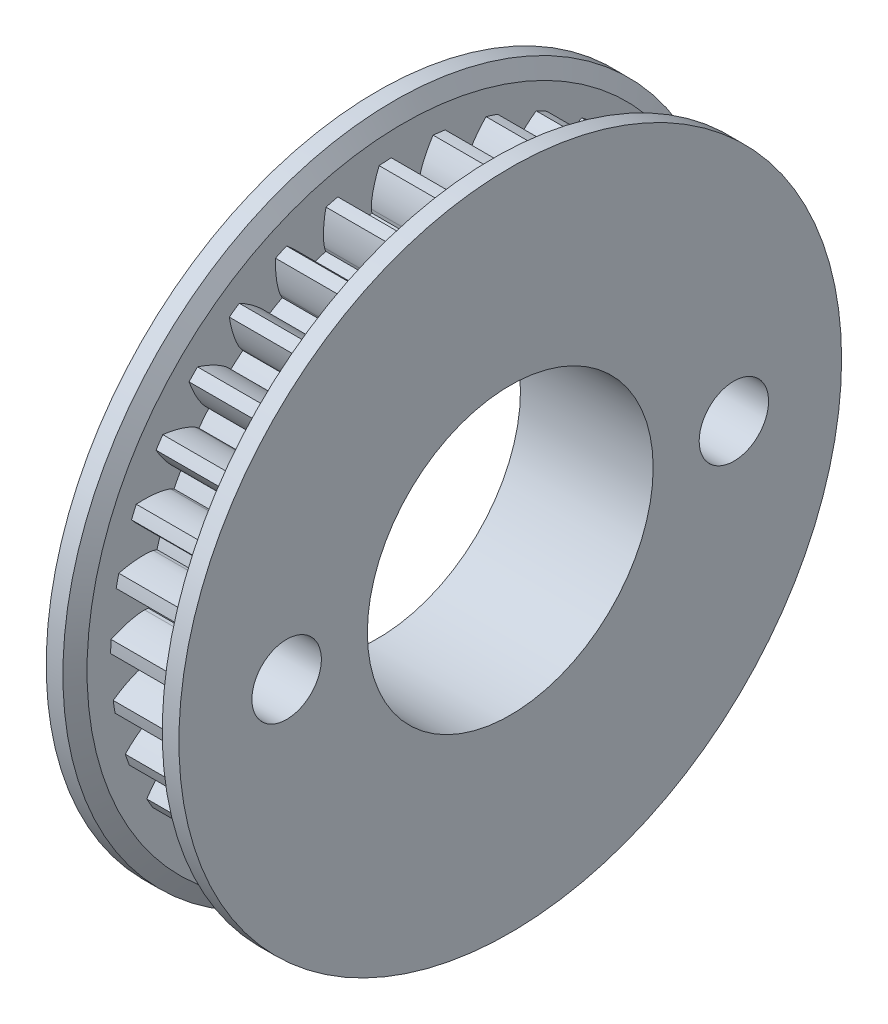
SolidWorks part; units mm, degrees
material "6061-T6 (SS)"
ref_plane "Front Plane" through (0, 0, 0) normal (1, 0, 0) x (0, 1, 0)
ref_plane "Top Plane" through (0, 0, 0) normal (0, 0, 1) x (0, 1, 0)
ref_plane "Right Plane" through (0, 0, 0) normal (0, 1, 0) x (-1, 0, 0)
sketch "Sketch1" plane through (0, 0, 0) normal (1, 0, 0) x (0, 1, 0)
  circle A0 centre (0, 0) radius 14.3239
  circle A1 centre (0, 0) radius 12.7123 construction
  circle A2 centre (0, 0) radius 12.5335 construction
  circle A3 centre (0, 0) radius 13.5282 construction
  dimension "D1" = 28.6479
  dimension "D2" = 25.4246
  dimension "D3" = 25.0669
  dimension "D4" = 27.0563
extrude "Boss-Extrude1" add sketch "Sketch1" along normal blind 4
sketch "Sketch3" plane through (4, 0, 0) normal (1, 0, 0) x (0, 1, 0)
  line L0 (0, 0) -> (12.7123, 0) construction
  line L1 (0, 0) -> (13.5267, 0.2016) construction
  line L2 (0, 0) -> (13.5215, -0.4233) construction
  line L3 (13.5215, -0.4233) -> (12.7061, -0.3978)
  line L4 (13.5215, -0.4233) -> (17.5655, -0.5499)
  line L5 (17.5655, 3.8286) -> (17.5655, -0.5499)
  line L6 (12.7123, 0) -> (12.5335, 0)
  line L7 (12.7061, -0.3978) -> (12.5273, -0.3922)
  circle A0 centre (0, 0) radius 13.5282 construction
  circle A1 centre (0, 0) radius 12.7123 construction
  circle A2 centre (0, 0) radius 12.5335 construction
  arc A3 (12.5335, 0) -> (12.5273, -0.3922) centre (0, 0) cw
  spline S0 degree 4 poles (12.7123, 0) (12.7217, 0.0002) (12.7481, 0.0014) (12.7977, 0.006) (12.8785, 0.017) (12.9807, 0.0361) (13.1119, 0.0665) (13.265, 0.1097) (13.4314, 0.1647) (13.6101, 0.2327) (13.7862, 0.3076) (13.9595, 0.3888) (14.13, 0.4756) (14.3336, 0.5875) (14.5737, 0.7311) (14.8479, 0.9123) (15.1507, 1.1332) (15.4498, 1.3745) (15.7361, 1.6249) (16.0155, 1.8923) (16.2787, 2.1612) (16.5412, 2.4544) (16.7778, 2.7322) (17.0301, 3.0582) (17.23, 3.3256) (17.4793, 3.6932) (17.6221, 3.9148) (17.7842, 4.1789) (17.8535, 4.2988) (17.8962, 4.3725) knots 0 0 0 0 0 0.005377 0.015084 0.028532 0.04661 0.064855 0.092111 0.119476 0.146842 0.174209 0.201575 0.228941 0.256307 0.307035 0.361767 0.4165 0.471232 0.525964 0.580697 0.635429 0.690161 0.744894 0.799626 0.854358 0.909091 0.954545 1 1 1 1 1 construction
  spline S1 degree 4 poles (12.7123, 0) (12.7217, 0.0002) (12.7481, 0.0014) (12.7977, 0.006) (12.8785, 0.017) (12.9807, 0.0361) (13.1119, 0.0665) (13.265, 0.1097) (13.4314, 0.1647) (13.6101, 0.2327) (13.7862, 0.3076) (13.9595, 0.3888) (14.13, 0.4756) (14.3336, 0.5875) (14.5737, 0.7311) (14.8479, 0.9123) (15.1507, 1.1332) (15.4498, 1.3745) (15.7361, 1.6249) (16.0155, 1.8923) (16.2787, 2.1612) (16.5412, 2.4544) (16.7778, 2.7322) (17.0301, 3.0582) (17.23, 3.3256) (17.4252, 3.6135) (17.5186, 3.7554) (17.5655, 3.8286) knots 0 0 0 0 0 0.005377 0.015084 0.028532 0.04661 0.064855 0.092111 0.119476 0.146842 0.174209 0.201575 0.228941 0.256307 0.307035 0.361767 0.4165 0.471232 0.525964 0.580697 0.635429 0.690161 0.744894 0.799626 0.854358 0.909091 0.909091 0.909091 0.909091 0.909091
  circle M1 centre (0, 0) radius 14.3239
  dimension "D1" = 2.647
extrude "Cut-Extrude1" cut sketch "Sketch3" against normal through all contours S1 L6 A3 L3 L4 M1 region at (4, 13.5838, -0.083)
mirror "Mirror1" about plane through (0, 0, 0) normal (0, 0.0313, 0.9995) of "Cut-Extrude1"
pattern_circular "CirPattern6" count 34 over 360 about axis through (4, 0, 0) along (-1, 0, 0) of "Cut-Extrude1", "Mirror1"
sketch "Sketch5" plane through (0, 0, 0) normal (0, 1, 0) x (-1, 0, 0)
  line L0 (-15.044, 0) -> (9.7198, 0) construction
  line L1 (-4, 0) -> (-5.25, 0)
  line L2 (-5.25, 0) -> (-5.25, 16.2306)
  line L4 (-4, 15.4806) -> (-4, 0)
  line L5 (0, 0) -> (1.25, 0)
  line L6 (0, 12.5335) -> (0, -12.5335) construction
  line L7 (1.25, 0) -> (1.25, 16.2306)
  line L9 (0, 15.4806) -> (0, 0)
  line L10 (-5.25, 16.2306) -> (-4.433, 16.2306)
  line L11 (-4.433, 16.2306) -> (-4, 15.4806)
  line L12 (0, 15.4806) -> (0.433, 16.2306)
  line L13 (0.433, 16.2306) -> (1.25, 16.2306)
  dimension "D1" = 150
  dimension "D2" = 150
  dimension "D4" = 0.75
  dimension "D5" = 1.25
  dimension "D6" = 1.25
  dimension "D3" = 16.2306
revolve "Revolve1" add sketch "Sketch5" angle 360 about L0
sketch "Sketch6" plane through (-1.25, 0, 0) normal (-1, 0, 0) x (0, -1, 0)
  circle A0 centre (0, 0) radius 7
  dimension "D1" = 14
extrude "Cut-Extrude2" cut sketch "Sketch6" against normal through all
sketch "Sketch7" plane through (0, 0, 0) normal (1, 0, 0) x (0, 1, 0)
  line L0 (0, -10.9537) -> (0, 10.9537) construction
  circle A0 centre (0, 10.9537) radius 1.5
  circle A1 centre (0, -10.9537) radius 1.5
  point P5 (0, 0)
  dimension "D2" = 21.9075
hole_wizard "M3 Clearance Hole1" positions "Sketch8" profile "Sketch9" hole size "M3" standard "ANSI Metric"
sketch "Sketch8" plane through (-1.25, 0, 0) normal (-1, 0, 0) x (0, 0, 1)
  point P0 (10.9537, 0)
  point P3 (-10.9537, 0)
sketch "Sketch9" plane through (-1.25, 0, 10.9537) normal (0, 1, 0) x (0, 0, 1)
  line L0 (0, 0) -> (0, 26.4215)
  line L1 (0, 26.4215) -> (1.7, 25.4)
  line L2 (1.7, 25.4) -> (1.7, 0)
  line L5 (1.7, 0) -> (0, 0)
  line L10 (0, 26.4215) -> (-1.7, 25.4) construction
  line L11 (0, -6.35) -> (0, 107.95) construction
  dimension "Hole Dia." = 3.4
  dimension "Hole Depth" = 25.4
  dimension "Drill Angle" = 118
equation "\"DiametralPitch\"= pi / \"Pitch\""
equation "\"NumberTeeth\"= 34"
equation "\"PressureAngle\"= 20"
equation "\"PitchDiameter\"= \"NumberTeeth\" / \"DiametralPitch\""
equation "\"BaseDiameter\"= \"PitchDiameter\" * cos ( \"PressureAngle\" )"
equation "\"Addendum\"= 1 / \"DiametralPitch\""
equation "\"Dedendum\"= 1.25 / \"DiametralPitch\""
equation "\"AddendumDiameter\"= \"PitchDiameter\" + \"Addendum\" + \"Addendum\""
equation "\"DedendumDiameter\"= \"PitchDiameter\" - \"Dedendum\" - \"Dedendum\""
equation "\"ToothSpacing\"= 360 / ( 4 * \"NumberTeeth\" )"
equation "\"D1@Sketch1\"=\"AddendumDiameter\""
equation "\"D2@Sketch1\"=\"BaseDiameter\""
equation "\"D3@Sketch1\"=\"DedendumDiameter\""
equation "\"D4@Sketch1\"=\"PitchDiameter\""
equation "\"D1@Sketch3\"=\"ToothSpacing\""
equation "\"D1@CirPattern6\"=\"NumberTeeth\""
equation "\"Pitch\"= 2.5"
equation "\"D2@Sketch7\"=0.8625in"
equation "\"D3@Sketch5\"=0.639in"
